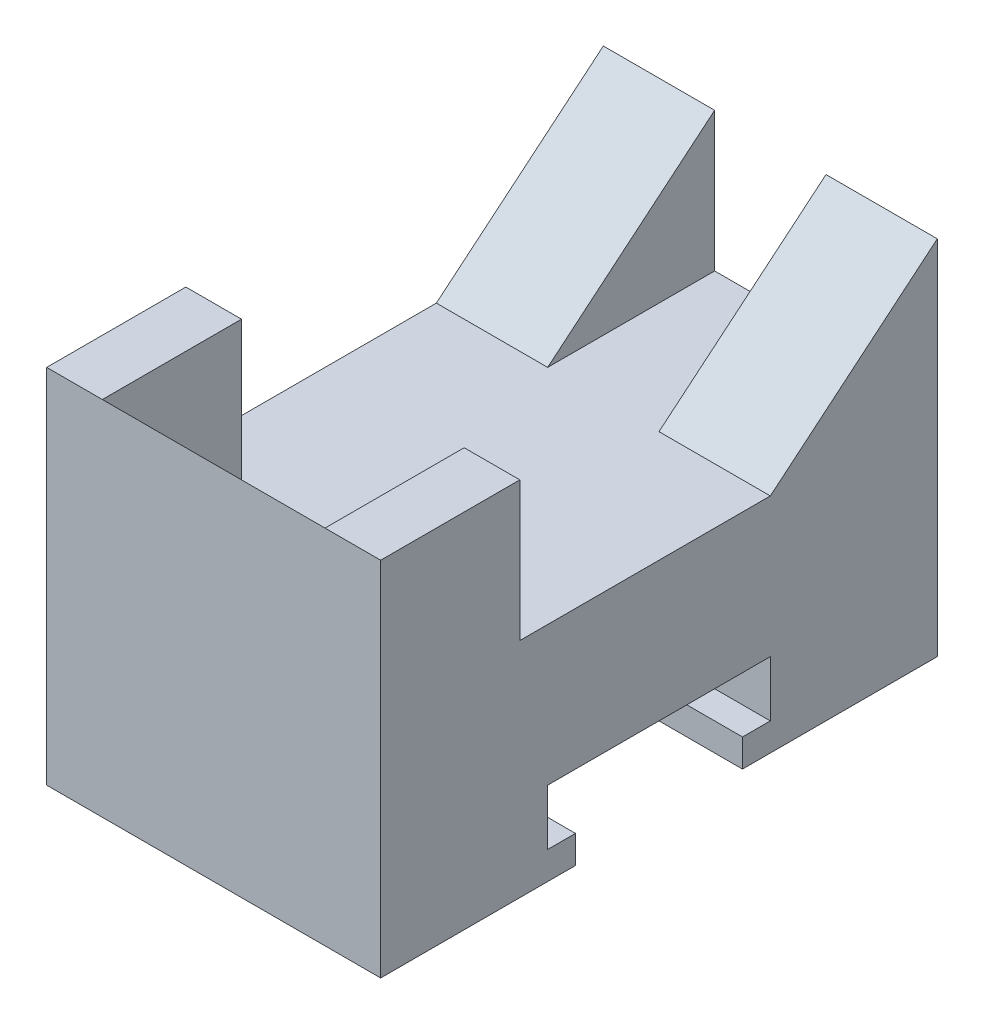
SolidWorks part; units mm, degrees
ref_plane "Front Plane" through (0, 0, 0) normal (0, 0, 1) x (1, 0, 0)
ref_plane "Top Plane" through (0, 0, 0) normal (0, 1, 0) x (1, 0, 0)
ref_plane "Right Plane" through (0, 0, 0) normal (1, 0, 0) x (0, 0, -1)
sketch "Sketch1" plane through (0, 0, 0) normal (1, 0, 0) x (0, 0, -1)
  line L0 (0, 0) -> (-175, 0)
  line L1 (-175, 0) -> (-175, 25)
  line L2 (-175, 25) -> (-150, 25)
  line L3 (-150, 25) -> (-150, 75)
  line L4 (-150, 75) -> (-350, 75)
  line L5 (-350, 75) -> (-350, 25)
  line L6 (-350, 25) -> (-325, 25)
  line L7 (-325, 25) -> (-325, 0)
  line L8 (-325, 0) -> (-500, 0)
  line L9 (-500, 0) -> (-500, 325)
  line L10 (-500, 325) -> (-375, 200)
  line L11 (-375, 200) -> (-150, 200)
  line L12 (-150, 200) -> (0, 325)
  line L13 (0, 325) -> (0, 0)
  point P15 (-375, 203.9256)
  point P16 (-325, 12.5)
  dimension "D1" = 500
  dimension "D2" = 350
  dimension "D3" = 175
  dimension "D4" = 150
  dimension "D5" = 150
  dimension "D6" = 75
  dimension "D7" = 25
  dimension "D9" = 325
  dimension "D10" = 200
  dimension "D11" = 225
  dimension "D12" = 45
extrude "Boss-Extrude1" add sketch "Sketch1" along normal blind 150 and the other way blind 150
sketch "Sketch3" plane through (0, 200, 0) normal (0, 1, 0) x (1, 0, 0)
  line L0 (150, -375) -> (150, -500)
  line L1 (150, -500) -> (100, -500)
  line L2 (-150, -500) -> (150, -500) construction
  line L3 (100, -500) -> (100, -375)
  line L4 (-150, -375) -> (150, -375) construction
  line L5 (100, -375) -> (150, -375)
  line L6 (0, -500) -> (0, -375) construction
  line L7 (-150, -500) -> (-100, -500)
  line L8 (-150, -375) -> (-150, -500)
  line L9 (-100, -375) -> (-150, -375)
  line L10 (-100, -500) -> (-100, -375)
  dimension "D1" = 50
extrude "Boss-Extrude2" add sketch "Sketch3" along normal blind 125
sketch "Sketch4" plane through (0, 0, 0) normal (0, 0, -1) x (-1, 0, 0)
  line L0 (0, 325) -> (0, 0) construction
  line L1 (150, 325) -> (-150, 325) construction
  line L2 (50, 325) -> (-50, 325)
  line L3 (-50, 325) -> (-50, 200)
  line L4 (-50, 200) -> (50, 200)
  line L5 (50, 325) -> (50, 200)
  point P9 (0, 200)
  dimension "D1" = 50
  dimension "D2" = 125
extrude "Cut-Extrude1" cut sketch "Sketch4" against normal blind 230
